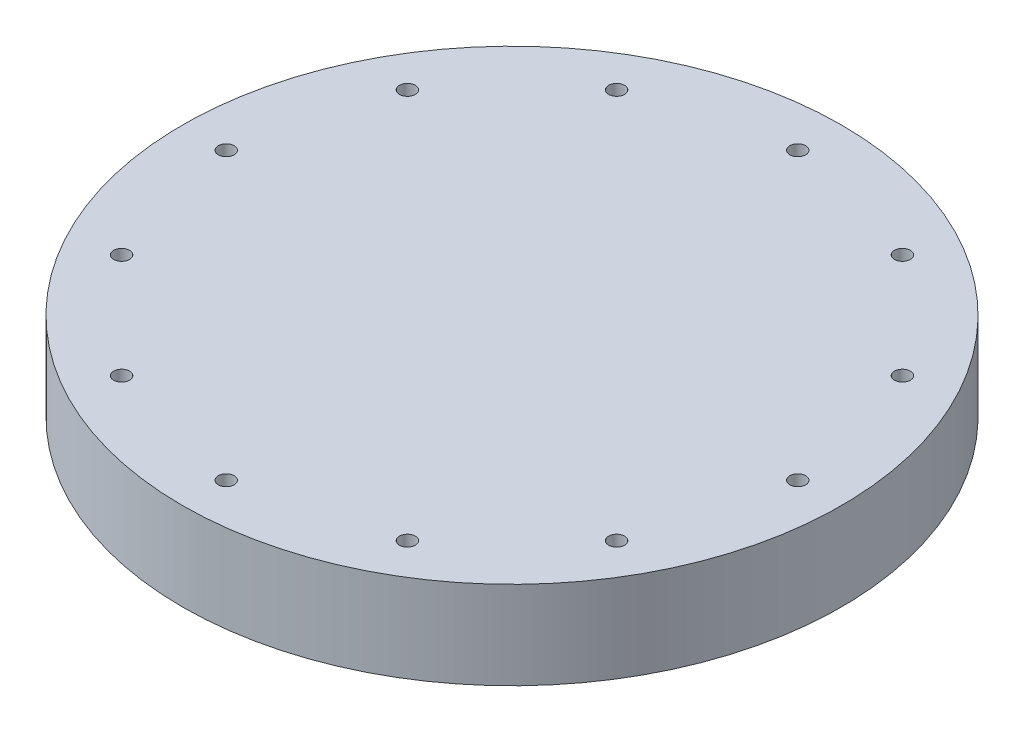
SolidWorks part; units mm, degrees
material "7075-T6 (SN)"
ref_plane "Front Plane" through (0, 0, 0) normal (0, 0, 1) x (1, 0, 0)
ref_plane "Top Plane" through (0, 0, 0) normal (0, 1, 0) x (1, 0, 0)
ref_plane "Right Plane" through (0, 0, 0) normal (1, 0, 0) x (0, 0, -1)
sketch "Sketch2" plane through (0, 0, 0) normal (0, 1, 0) x (1, 0, 0)
  circle A1 centre (0, 0) radius 25.4
  dimension "D1" = 50.8
extrude "Base Cylinder" add sketch "Sketch2" along normal blind 19.05
sketch "Sketch3" plane through (0, 0, 0) normal (0, -1, 0) x (1, 0, 0)
  circle A1 centre (0, 0) radius 59.5312
  dimension "D1" = 119.0625
extrude "Aft Flange" add sketch "Sketch3" against normal blind 9.525
sketch "Sketch For Bolt Holes" plane through (0, 0, 0) normal (0, -1, 0) x (1, 0, 0)
  circle A0 centre (-51.6255, 0) radius 1.5875
  circle A1 centre (-44.709, 25.8128) radius 1.5875
  circle A2 centre (-25.8128, 44.709) radius 1.5875
  circle A3 centre (0, 51.6255) radius 1.5875
  circle A4 centre (25.8127, 44.709) radius 1.5875
  circle A5 centre (44.709, 25.8128) radius 1.5875
  circle A6 centre (51.6255, 0) radius 1.5875
  circle A7 centre (44.709, -25.8127) radius 1.5875
  circle A8 centre (25.8128, -44.709) radius 1.5875
  circle A9 centre (0, -51.6255) radius 1.5875
  circle A10 centre (-25.8127, -44.709) radius 1.5875
  circle A11 centre (-44.709, -25.8128) radius 1.5875
  point P36 (0, 0)
  dimension "D2" = 3.175
  dimension "D1" = 51.6255
  dimension "D3" = 12
hole_wizard "Bolt Circle" positions "Sketch8" profile "Sketch9" hole size "#4-40" standard "ANSI Inch" end condition up to next
sketch "Sketch8" plane through (0, 0, 0) normal (0, -1, 0) x (-1, 0, 0)
  point P0 (-25.8127, -44.709)
  point P3 (-44.709, -25.8128)
  point P6 (-51.6255, 0)
  point P9 (-44.709, 25.8127)
  point P12 (-25.8128, 44.709)
  point P15 (0, 51.6255)
  point P18 (25.8127, 44.709)
  point P21 (44.709, 25.8128)
  point P24 (51.6255, 0)
  point P27 (44.709, -25.8128)
  point P30 (25.8128, -44.709)
  point P33 (0, -51.6255)
  point P36 (-25.8127, -44.709)
  point P38 (-44.709, -25.8128)
  point P40 (-51.6255, 0)
sketch "Sketch9" plane through (25.8127, 0, 44.709) normal (1, 0, 0) x (0, 0, -1)
  line L0 (0, 0) -> (0, 9.525)
  line L1 (0, 9.525) -> (1.4351, 9.525)
  line L2 (1.4351, 9.525) -> (1.4351, 0)
  line L5 (1.4351, 0) -> (0, 0)
  line L11 (0, -6.35) -> (0, 107.95) construction
  dimension "Thru Hole Dia." = 2.8702
  dimension "Thru Hole Depth" = 9.525
sketch "Sketch18" plane through (0, 0, 0) normal (0, -1, 0) x (1, 0, 0)
  circle A0 centre (0, 0) radius 59.5312
extrude "Boss-Extrude1" add sketch "Sketch18" along normal blind 6.35
sketch "Sketch19" plane through (0, -6.35, 0) normal (0, -1, 0) x (1, 0, 0)
  circle A3 centre (0, 0) radius 56.4134
  dimension "D1" = 112.8268
extrude "Cut-Extrude1" cut sketch "Sketch19" against normal blind 6.35
sketch "Sketch20" plane through (0, 0, 0) normal (0, 0, 1) x (1, 0, 0)
  line L0 (59.5312, 9.525) -> (-59.5312, 9.525) construction
  line L1 (-39.6604, 25.9889) -> (32.2639, 25.9889)
  line L2 (-39.6604, 25.9889) -> (-39.6604, 9.525)
  line L3 (-39.6604, 9.525) -> (32.2639, 9.525)
  line L4 (32.2639, 25.9889) -> (32.2639, 9.525)
extrude "Cut-Extrude2" cut sketch "Sketch20" against normal mid plane 304.8
